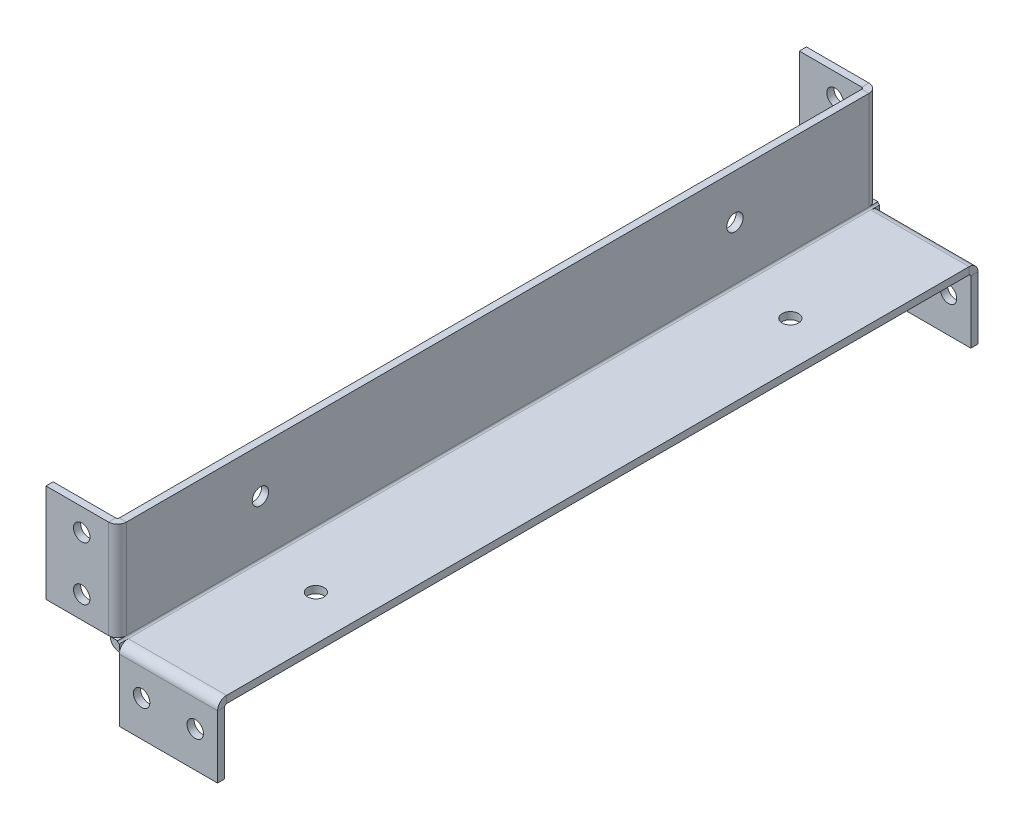
SolidWorks part; units mm, degrees
note: The reader was unsure of these and kept them because the rebuilt part matched: flange length of "Edge-Flange1", "Edge-Flange2".
ref_plane "Front Plane" through (0, 0, 0) normal (0, 0, 1) x (1, 0, 0)
ref_plane "Top Plane" through (0, 0, 0) normal (0, 1, 0) x (1, 0, 0)
ref_plane "Right Plane" through (0, 0, 0) normal (1, 0, 0) x (0, 0, -1)
sketch "Sketch1" plane through (0, 0, 0) normal (0, 1, 0) x (1, 0, 0)
  line L1 (30, 212.75) -> (-30, 212.75)
  line L2 (30, 212.75) -> (30, -212.75)
  line L3 (30, -212.75) -> (-30, -212.75)
  line L4 (-30, 212.75) -> (-30, -212.75)
  line L5 (30, 212.75) -> (-30, -212.75) construction
  line L6 (30, -212.75) -> (-30, 212.75) construction
  point P0 (0, 0)
  dimension "D1" = 60
  dimension "D2" = 425.5
sheet metal parameters "Sheet-Metal1" thickness 4 parameters "D1"=1
base flange "Base-Flange1" sketch "Sketch1" thickness 4 reverse thickness direction yes parameters "D1"=1
edge flange "Edge-Flange1" sketch "Sketch5" flange angle 90 flange length 60 flange position material inside bend radius 1 thickness 4 parameters "D6"=10
sketch "Sketch5" plane through (-30, 4, 0) normal (-1, 0, 0) x (0, 0, 1)
  line L2 (-212.75, 0) -> (-212.75, 56)
  line L3 (-212.75, 56) -> (212.75, 56)
  line L4 (212.75, 56) -> (212.75, 0)
  line L5 (-212.75, 0) -> (212.75, 0) construction
  line L6 (-212.75, 0) -> (212.75, 0)
bend "EdgeBend1" bend radius 1 bend angle 90 parameters "D5"=1
edge flange "Edge-Flange2" sketch "Sketch14" flange profiles "Sketch14", "Sketch15", "Sketch16", "Sketch17" flange angle 90 flange length 40 flange position material inside bend radius 1 thickness 4 relief none parameters "D6"=10, "D8"=0.5
sketch "Sketch14" plane through (-30, 0, 212.75) normal (0, 0, -1) x (0, -1, 0)
  line L1 (-5, 0) -> (-60, 0) construction
  line L2 (-60, 0) -> (-60, 36)
  line L3 (-60, 36) -> (-5, 36)
  line L4 (-5, 36) -> (-5, 0)
  line L5 (-5, 0) -> (-60, 0)
sketch "Sketch15" plane through (0, 0, 212.75) normal (0, 0, -1) x (1, 0, 0)
  line L0 (30, 0) -> (-25, 0) construction
  line L1 (30, 0) -> (-25, 0)
  line L2 (30, 0) -> (30, 36)
  line L3 (30, 36) -> (-25, 36)
  line L4 (-25, 36) -> (-25, 0)
sketch "Sketch16" plane through (-30, 0, -212.75) normal (0, 0, 1) x (0, 1, 0)
  line L0 (60, 0) -> (5, 0) construction
  line L1 (60, 0) -> (5, 0)
  line L2 (60, 0) -> (60, 36)
  line L3 (60, 36) -> (5, 36)
  line L4 (5, 36) -> (5, 0)
sketch "Sketch17" plane through (0, 0, -212.75) normal (0, 0, 1) x (-1, 0, 0)
  line L0 (25, 0) -> (-30, 0) construction
  line L1 (25, 0) -> (-30, 0)
  line L2 (25, 0) -> (25, 36)
  line L3 (25, 36) -> (-30, 36)
  line L4 (-30, 36) -> (-30, 0)
bend "EdgeBend2" bend radius 1 bend angle 90 parameters "D5"=2
bend "EdgeBend3" bend radius 1 bend angle 90 parameters "D5"=3
bend "EdgeBend4" bend radius 1 bend angle 90 parameters "D5"=4
bend "EdgeBend5" bend radius 1 bend angle 90 parameters "D5"=5
sketch "Sketch18" plane through (0, 0, 212.75) normal (0, 0, 1) x (1, 0, 0)
  line L0 (-25, 4) -> (30, 4) construction
  line L1 (-26, 60) -> (-26, 5) construction
  line L2 (-66, 60) -> (-31, 60) construction
  line L3 (30, -1) -> (30, -36) construction
  circle A0 centre (-46, 47.5) radius 4.6
  circle A1 centre (-46, 17.5) radius 4.6
  circle A2 centre (-12.5, -16) radius 4.6
  circle A3 centre (17.5, -16) radius 4.6
  dimension "D7" = 9.2
  dimension "D1" = 30
  dimension "D2" = 30
  dimension "D3" = 20
  dimension "D4" = 20
  dimension "D5" = 12.5
  dimension "D6" = 12.5
extrude "Extrude1" cut sketch "Sketch18" against normal through all normal cut yes
sketch "Sketch19" plane through (-26, 0, 0) normal (1, 0, 0) x (0, 0, -1)
  line L0 (-207.75, 60) -> (207.75, 60) construction
  line L1 (-212.75, 5) -> (-212.75, 60) construction
  line L2 (212.75, 5) -> (212.75, 60) construction
  circle A0 centre (-132.75, 35) radius 4.6
  circle A1 centre (132.75, 35) radius 4.6
  dimension "D4" = 9.2
  dimension "D1" = 25
  dimension "D2" = 80
  dimension "D3" = 80
extrude "Extrude2" cut sketch "Sketch19" against normal blind 4 normal cut yes
sketch "Sketch20" plane through (0, 4, 0) normal (0, 1, 0) x (1, 0, 0)
  line L0 (30, -207.75) -> (30, 207.75) construction
  line L1 (-25, -212.75) -> (30, -212.75) construction
  line L2 (30, 212.75) -> (-25, 212.75) construction
  circle A0 centre (5, 132.75) radius 4.6
  circle A1 centre (5, -132.75) radius 4.6
  dimension "D2" = 9.2
  dimension "D1" = 25
  dimension "D3" = 80
  dimension "D4" = 80
extrude "Extrude3" cut sketch "Sketch20" against normal blind 4 normal cut yes
flat pattern "Flat-Pattern1" [suppressed]
sketch "Bend-Lines1" plane through (0, 4, 0) normal (0, 1, 0) x (-1, 0, 0)
  line L0 (25, -199.4012) -> (-30, -199.4012) construction
  line L1 (82.8023, -199.4012) -> (27.8023, -199.4012) construction
  line L2 (-30, 199.4012) -> (25, 199.4012) construction
  line L3 (27.8023, 199.4012) -> (82.8023, 199.4012) construction
  line L4 (26.4012, -203) -> (26.4012, 203) construction
  line L5 (25, -199.4012) -> (-30, -199.4012) construction
  line L6 (82.8023, -199.4012) -> (27.8023, -199.4012) construction
  line L7 (-30, 199.4012) -> (25, 199.4012) construction
  line L8 (27.8023, 199.4012) -> (82.8023, 199.4012) construction
  line L9 (26.4012, -203) -> (26.4012, 203) construction
sketch3d "Bounding-Box1" [suppressed]
  line L0 (52.8023, 32.8023, 0) -> (52.8023, -438.8023, 0) construction
  line L1 (-60, 32.8023, 0) -> (-60, -438.8023, 0) construction
  line L2 (52.8023, 32.8023, 0) -> (-60, 32.8023, 0) construction
  line L3 (52.8023, -438.8023, 0) -> (-60, -438.8023, 0) construction
bend of the flat pattern "Flatten-<EdgeBend1>1"
bend of the flat pattern "Flatten-<EdgeBend2>1"
bend of the flat pattern "Flatten-<EdgeBend3>1"
bend of the flat pattern "Flatten-<EdgeBend4>1"
bend of the flat pattern "Flatten-<EdgeBend5>1"
